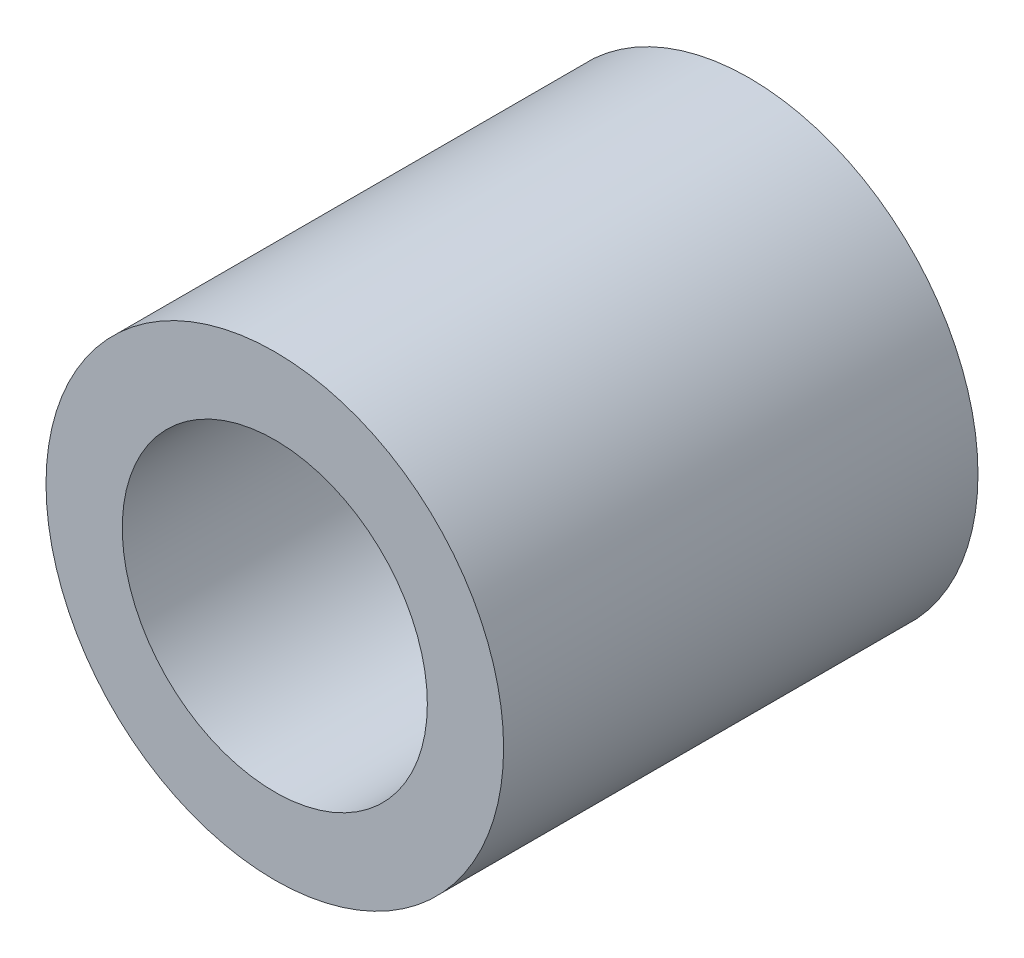
SolidWorks part; units mm, degrees
material "PET"
ref_plane "Front Plane" through (0, 0, 0) normal (0, 0, 1) x (1, 0, 0)
ref_plane "Top Plane" through (0, 0, 0) normal (0, 1, 0) x (1, 0, 0)
ref_plane "Right Plane" through (0, 0, 0) normal (1, 0, 0) x (0, 0, -1)
sketch "Sketch1" plane through (0, 0, 0) normal (0, 0, 1) x (1, 0, 0)
  circle A0 centre (0, 0) radius 6.35
  circle A1 centre (0, 0) radius 9.525
  dimension "D1" = 12.7
  dimension "D2" = 19.05
extrude "Boss-Extrude1" add sketch "Sketch1" along normal mid plane 19.7485
